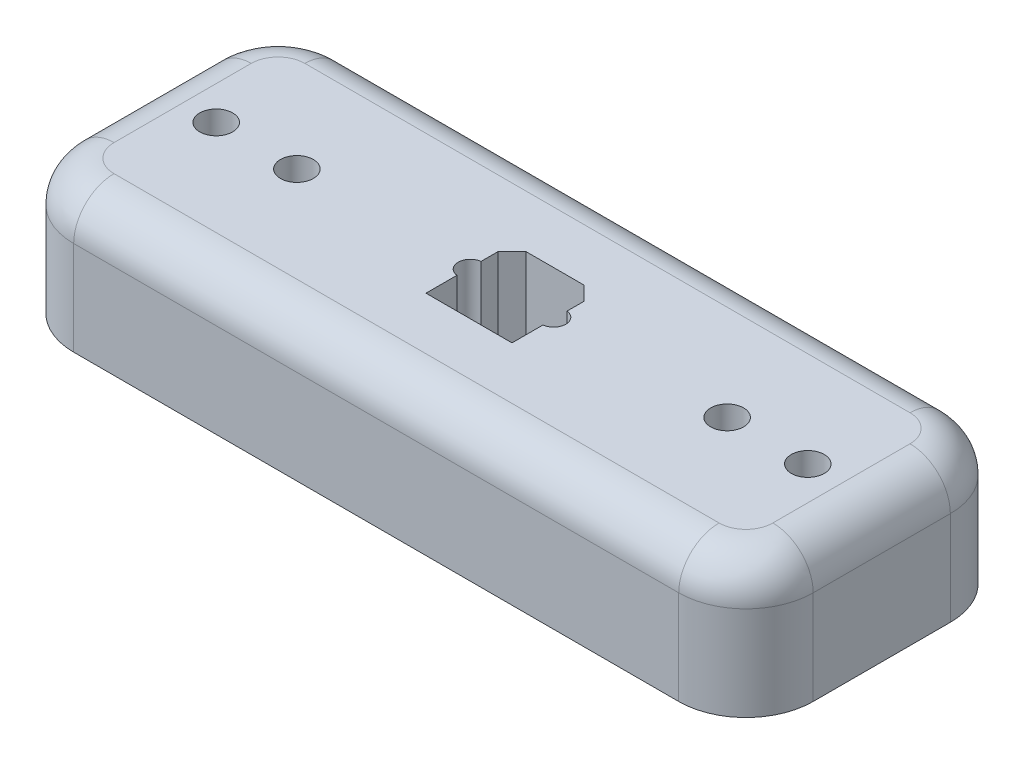
SolidWorks part; units mm, degrees
ref_plane "前视基准面" through (0, 0, 0) normal (0, 0, 1) x (1, 0, 0)
ref_plane "上视基准面" through (0, 0, 0) normal (0, 1, 0) x (1, 0, 0)
ref_plane "右视基准面" through (0, 0, 0) normal (1, 0, 0) x (0, 0, -1)
sketch "草图1" plane through (0, 0, 0) normal (0, 1, 0) x (1, 0, 0)
  line L0 (-27.5, 5.1) -> (-27.5, -5.1)
  line L1 (-10, 10) -> (10, 10) construction
  line L2 (-10, 10) -> (-10, -10) construction
  line L3 (-10, -10) -> (10, -10) construction
  line L4 (10, 10) -> (10, -10) construction
  line L5 (27.5, -5.1) -> (27.5, 5.1)
  line L6 (-22.5, -10.1) -> (22.5, -10.1)
  line L7 (22.5, 10.1) -> (-22.5, 10.1)
  line L8 (-3.1, -3.1) -> (3.1, -3.1) construction
  line L9 (3.1, -3.1) -> (3.1, -0.8) construction
  line L10 (-3.1, -3.1) -> (-3.1, -0.8) construction
  line L11 (-2.1, 3.1) -> (2.1, 3.1) construction
  line L12 (0, 3.1) -> (0, -3.1) construction
  line L13 (2.1, 3.1) -> (3.1, 2.1) construction
  line L14 (-2.1, 3.1) -> (-3.1, 2.1) construction
  line L15 (-20.6246, 0) -> (20.7431, 0) construction
  line L16 (-3.1, 0.8) -> (-3.1, 2.1) construction
  line L17 (3.1, 0.8) -> (3.1, 2.1) construction
  line L18 (-3.2, -3.2) -> (3.2, -3.2)
  line L19 (3.2, -3.2) -> (3.2, -0.8944)
  line L20 (3.2, 0.8944) -> (3.2, 2.1414)
  line L21 (2.1414, 3.2) -> (3.2, 2.1414)
  line L22 (-2.1414, 3.2) -> (2.1414, 3.2)
  line L23 (-2.1414, 3.2) -> (-3.2, 2.1414)
  line L24 (-3.2, 0.8944) -> (-3.2, 2.1414)
  line L25 (-3.2, -3.2) -> (-3.2, -0.8944)
  line L30 (-7.5, 7.5) -> (7.5, 7.5) construction
  line L31 (-7.5, 7.5) -> (-7.5, -7.5) construction
  line L32 (-7.5, -7.5) -> (7.5, -7.5) construction
  line L33 (7.5, 7.5) -> (7.5, -7.5) construction
  line L37 (-10.1, 10.1) -> (10.1, 10.1) construction
  line L38 (10.1, 10.1) -> (10.1, -10.1) construction
  line L39 (-10.1, -10.1) -> (10.1, -10.1) construction
  line L40 (-10.1, 10.1) -> (-10.1, -10.1) construction
  line L45 (-27.5, -15) -> (27.5, -15) construction
  line L46 (27.5, -15) -> (27.5, 15) construction
  line L47 (27.5, 15) -> (-27.5, 15) construction
  line L48 (-27.5, 15) -> (-27.5, -15) construction
  line L49 (-29.8378, 0) -> (33.7315, 0) construction
  line L50 (0, 23.8838) -> (0, -18.0336) construction
  circle A0 centre (-22, 0) radius 1.225
  circle A1 centre (22, 0) radius 1.225
  circle A2 centre (-16, 0) radius 1.225
  circle A3 centre (16, 0) radius 1.225
  arc A4 (3.1, -0.8) -> (3.1, 0.8) centre (3.1, 0) ccw construction
  arc A5 (-3.1, 0.8) -> (-3.1, -0.8) centre (-3.1, 0) ccw construction
  circle A6 centre (0, 0) radius 1.25
  arc A7 (3.2, -0.8944) -> (3.2, 0.8944) centre (3.1, 0) ccw
  arc A8 (-3.2, 0.8944) -> (-3.2, -0.8944) centre (-3.1, 0) ccw
  arc A9 (-27.5, -5.1) -> (-22.5, -10.1) centre (-22.5, -5.1) ccw
  arc A10 (27.5, -5.1) -> (22.5, -10.1) centre (22.5, -5.1) cw
  arc A11 (22.5, 10.1) -> (27.5, 5.1) centre (22.5, 5.1) cw
  arc A12 (-22.5, 10.1) -> (-27.5, 5.1) centre (-22.5, 5.1) ccw
  point P5 (0, 0)
  point P7 (0, 15)
  point P25 (-7.5, 0)
  point P26 (0, 7.5)
  point P56 (0, -3.1)
  point P57 (0, 3.1)
  point P62 (0, 0)
  point P65 (3.1, 0)
  point P66 (-3.1, 0)
  dimension "D10" = 2.45
  dimension "D17" = 1.6
  dimension "D19" = 2.5
  dimension "D21" = 5
  dimension "D1" = 20
  dimension "D2" = 30
  dimension "D3" = 55
  dimension "D4" = 15
  dimension "D5" = 2.5
  dimension "D6" = 2.5
  dimension "D9" = 6
  dimension "D11" = 6
  dimension "D12" = 12
  dimension "D13" = 12
  dimension "D7" = 5
  dimension "D14" = 6.2
  dimension "D15" = 5.2
  dimension "D16" = 6.2
  dimension "D18" = 4.2
  dimension "D8" = 0.1
  dimension "D20" = 0.1
extrude "凸台-拉伸1" add sketch "草图1" along normal blind 10 contours L7 A12 L0 A9 L6 A10 L5 A11 A0 A1 A2 A3 A8 L24 L23 L22 L21 L20 A7 L19 L18 L25 region at (-25.6212, 0, -8.2212)
extrude "凸台-拉伸2" add sketch "草图1<7>" along normal blind 2.5 contours L24 A8 L25 L18 L19 A7 L20 L21 L22 L23 A6 region at (-3.0976, 0, 2.0472)
sketch "草图1<7>" plane through (0, 0, 0) normal (0, 1, 0) x (1, 0, 0) same geometry as "草图1"
fillet "圆角1" radius 3 8 edges at (-26.0355, 10, 8.6355) (-26.0355, 10, -8.6355) (26.0355, 10, -8.6355) (26.0355, 10, 8.6355) (-27.5, 10, 0) (27.5, 10, 0) (0, 10, -10.1) (0, 10, 10.1)
